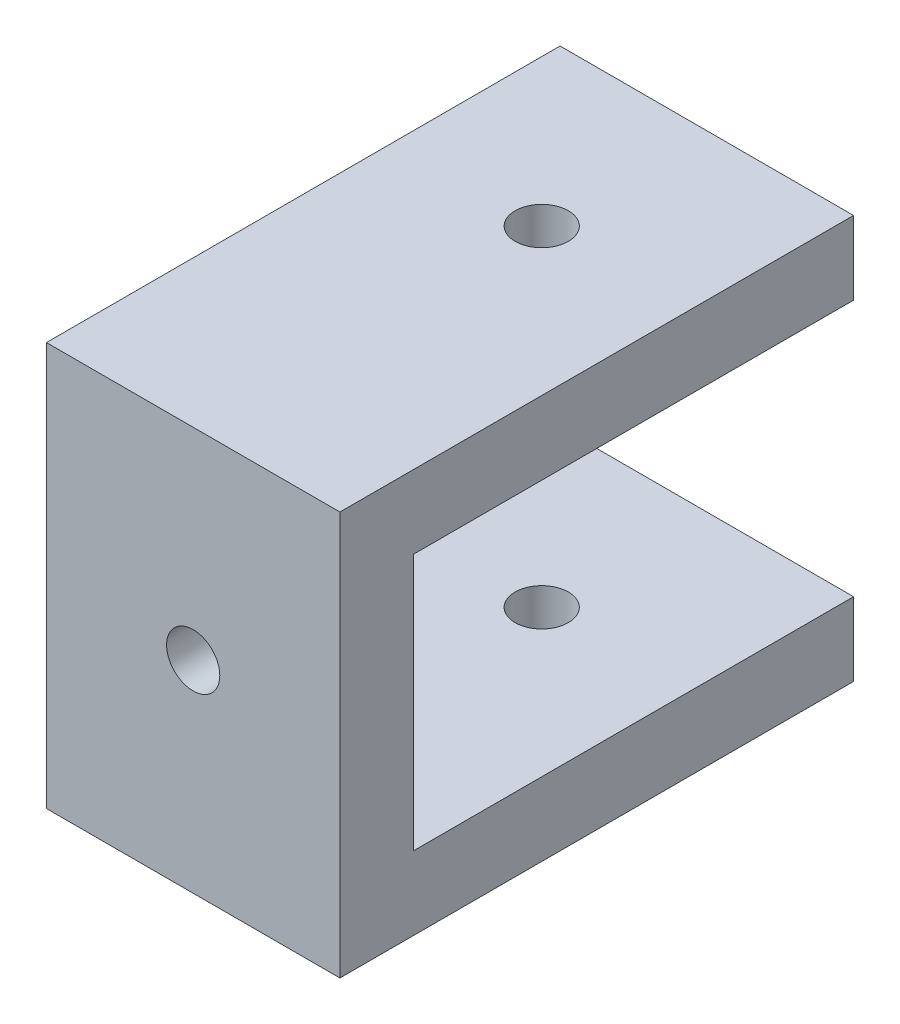
SolidWorks part; units mm, degrees
ref_plane "Front Plane" through (0, 0, 0) normal (0, 0, 1) x (1, 0, 0)
ref_plane "Top Plane" through (0, 0, 0) normal (0, 1, 0) x (1, 0, 0)
ref_plane "Right Plane" through (0, 0, 0) normal (1, 0, 0) x (0, 0, -1)
sketch "Sketch1" plane through (0, 0, 0) normal (1, 0, 0) x (0, 0, -1)
  line L0 (0, 8.89) -> (0, -8.89)
  line L1 (0, -8.89) -> (30.48, -8.89)
  line L2 (30.48, -8.89) -> (30.48, -13.97)
  line L3 (30.48, -13.97) -> (-5.08, -13.97)
  line L4 (-5.08, -13.97) -> (-5.08, 13.97)
  line L5 (-5.08, 13.97) -> (30.48, 13.97)
  line L6 (30.48, 13.97) -> (30.48, 8.89)
  line L7 (30.48, 8.89) -> (0, 8.89)
  point P8 (0, 0)
  dimension "D1" = 5.08
  dimension "D2" = 5.08
  dimension "D3" = 30.48
  dimension "D4" = 17.78
extrude "Boss-Extrude1" add sketch "Sketch1" along normal blind 20.32
sketch "Sketch2" plane through (0, 0, 5.08) normal (0, 0, 1) x (1, 0, 0)
  line L1 (20.32, 13.97) -> (20.32, -13.97) construction
  circle A0 centre (10.16, 0) radius 1.8415
  point P2 (0, 0)
  point P7 (0, 0)
  dimension "D1" = 3.683
  dimension "D2" = 10.16
extrude "Cut-Extrude1" cut sketch "Sketch2" against normal up to next
sketch "Sketch3" plane through (0, 13.97, 0) normal (0, 1, 0) x (1, 0, 0)
  line L0 (20.32, -5.08) -> (0, -5.08) construction
  line L1 (20.32, 30.48) -> (20.32, -5.08) construction
  circle A0 centre (10.16, 19.05) radius 1.8415
  point P2 (0, 0)
  point P6 (0, 0)
  dimension "D1" = 3.683
  dimension "D2" = 24.13
  dimension "D3" = 10.16
extrude "Cut-Extrude2" cut sketch "Sketch3" against normal through all and the other way through all
